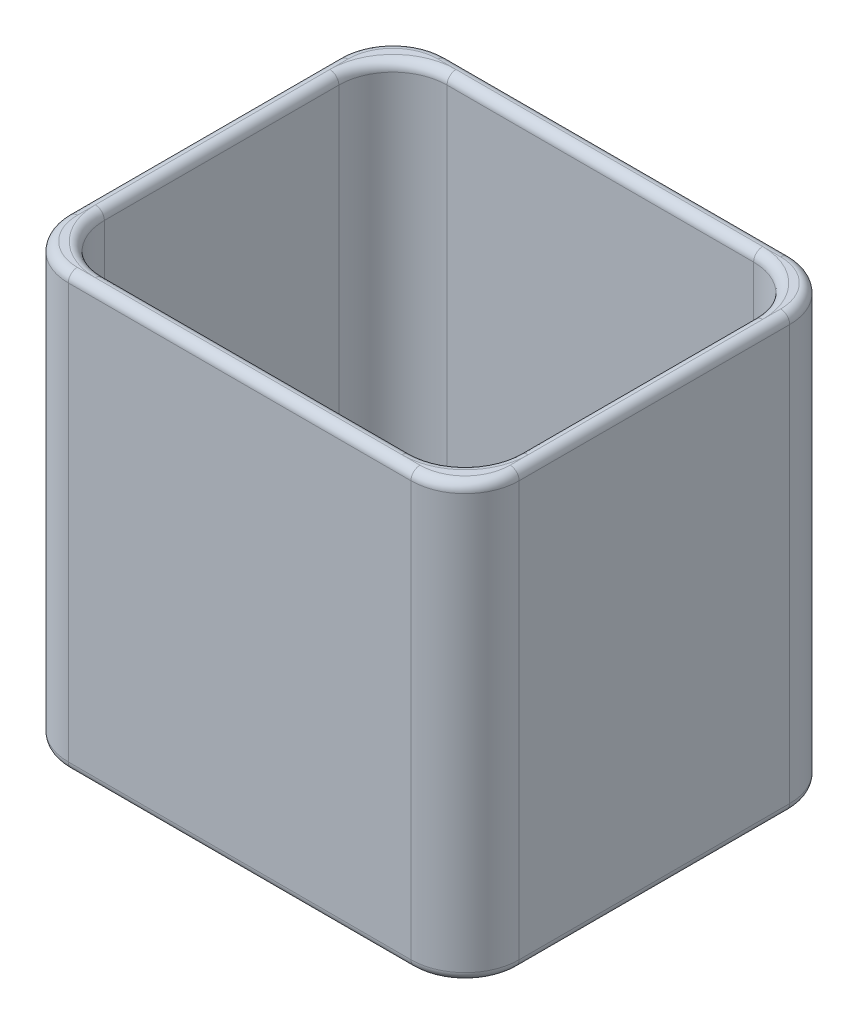
SolidWorks part; units mm, degrees
ref_plane "Front Plane" through (0, 0, 0) normal (0, 0, 1) x (1, 0, 0)
ref_plane "Top Plane" through (0, 0, 0) normal (0, 1, 0) x (1, 0, 0)
ref_plane "Right Plane" through (0, 0, 0) normal (1, 0, 0) x (0, 0, -1)
sketch "Sketch1" plane through (0, 0, 0) normal (0, 1, 0) x (1, 0, 0)
  line L1 (-36.5125, -30.1625) -> (36.5125, -30.1625)
  line L2 (-36.5125, -30.1625) -> (-36.5125, 30.1625)
  line L3 (-36.5125, 30.1625) -> (36.5125, 30.1625)
  line L4 (36.5125, -30.1625) -> (36.5125, 30.1625)
  line L5 (-36.5125, -30.1625) -> (36.5125, 30.1625) construction
  line L6 (-36.5125, 30.1625) -> (36.5125, -30.1625) construction
  point P0 (0, 0)
  dimension "D1" = 73.025
  dimension "D2" = 60.325
extrude "Extrude-Thin1" add sketch "Sketch1" along normal blind 73.025 thin thin type one direction wall 3.175
fillet "Fillet1" radius 9.525 8 edges at (-36.5125, 36.5125, 30.1625) (36.5125, 36.5125, 30.1625) (36.5125, 36.5125, -30.1625) (39.6875, 36.5125, 33.3375) (-39.6875, 36.5125, 33.3375) (-39.6875, 36.5125, -33.3375) (39.6875, 36.5125, -33.3375) (-36.5125, 36.5125, -30.1625)
sketch "Sketch2" plane through (0, 0, 0) normal (0, -1, 0) x (1, 0, 0)
  line L4 (39.6875, -23.8125) -> (39.6875, 23.8125)
  line L5 (30.1625, 33.3375) -> (-30.1625, 33.3375)
  line L6 (-39.6875, 23.8125) -> (-39.6875, -23.8125)
  line L7 (-30.1625, -33.3375) -> (30.1625, -33.3375)
  line L8 (39.6875, -23.8125) -> (39.6875, 23.8125)
  line L9 (30.1625, 33.3375) -> (-30.1625, 33.3375)
  line L10 (-39.6875, 23.8125) -> (-39.6875, -23.8125)
  line L11 (-30.1625, -33.3375) -> (30.1625, -33.3375)
  arc A4 (39.6875, 23.8125) -> (30.1625, 33.3375) centre (30.1625, 23.8125) ccw
  arc A5 (-30.1625, 33.3375) -> (-39.6875, 23.8125) centre (-30.1625, 23.8125) ccw
  arc A6 (-39.6875, -23.8125) -> (-30.1625, -33.3375) centre (-30.1625, -23.8125) ccw
  arc A7 (30.1625, -33.3375) -> (39.6875, -23.8125) centre (30.1625, -23.8125) ccw
  arc A8 (39.6875, 23.8125) -> (30.1625, 33.3375) centre (30.1625, 23.8125) ccw
  arc A9 (-30.1625, 33.3375) -> (-39.6875, 23.8125) centre (-30.1625, 23.8125) ccw
  arc A10 (-39.6875, -23.8125) -> (-30.1625, -33.3375) centre (-30.1625, -23.8125) ccw
  arc A11 (30.1625, -33.3375) -> (39.6875, -23.8125) centre (30.1625, -23.8125) ccw
  dimension "D1" = 0
extrude "Boss-Extrude1" add sketch "Sketch2" along normal blind 3.175
fillet "Fillet2" radius 6.35 8 edges at (0, 0, -30.1625) (33.7227, 0, -27.3727) (36.5125, 0, 0) (33.7227, 0, 27.3727) (0, 0, 30.1625) (-33.7227, 0, 27.3727) (-36.5125, 0, 0) (-33.7227, 0, -27.3727)
fillet "Fillet3" radius 1.5875 24 edges at (-36.8977, 73.025, 30.5477) (-39.6875, 73.025, 0) (-36.8977, 73.025, -30.5477) (0, 73.025, -33.3375) (36.8977, 73.025, -30.5477) (39.6875, 73.025, 0) (36.8977, 73.025, 30.5477) (-33.7227, 73.025, -27.3727) (0, 73.025, -30.1625) (33.7227, 73.025, -27.3727) (36.5125, 73.025, 0) (33.7227, 73.025, 27.3727) (0, 73.025, 30.1625) (-33.7227, 73.025, 27.3727) (0, 73.025, 33.3375) (-36.5125, 73.025, 0) (-36.8977, -3.175, 30.5477) (0, -3.175, 33.3375) (36.8977, -3.175, 30.5477) (39.6875, -3.175, 0) (36.8977, -3.175, -30.5477) (0, -3.175, -33.3375) (-36.8977, -3.175, -30.5477) (-39.6875, -3.175, 0)
sketch "Sketch3" plane through (0, 0, 0) normal (0, 1, 0) x (1, 0, 0)
  line L0 (-25.4, 19.05) -> (-26.9875, 20.6375) construction
  line L1 (0, 0) -> (-25.4, 0) construction
  line L2 (0, 0) -> (0, 19.05) construction
  line L3 (0, 19.05) -> (-25.4, 19.05) construction
  line L4 (-25.4, 0) -> (-25.4, 19.05) construction
  point P5 (-26.9875, 20.6375)
  dimension "D1" = 45
  dimension "D2" = 1.5875
ref_axis "Axis1" through (-25.4, 0, -19.05) along (0, 1, 0)
ref_plane "Plane1" through (0, 0, -19.05) normal (0, 0, -1) x (0, 1, 0)
sketch "Sketch4" plane through (0, 0, -19.05) normal (0, 0, -1) x (0, 1, 0)
  line L0 (-3.175, -23.3362) -> (-1.24, -23.3362)
  line L1 (-3.175, -30.1625) -> (-3.175, 30.1625) construction
  line L2 (-1.24, -23.3362) -> (0, -21.2725)
  line L3 (0, -21.2725) -> (0, -25.4)
  line L4 (0, -25.4) -> (25.3633, -25.4) construction
  line L5 (0, -25.4) -> (-3.175, -25.4) construction
  line L6 (-3.175, -25.4) -> (-3.175, -23.3362)
  line L8 (0, 0) -> (0, -25.4) construction
  line L9 (0, -25.4) -> (-3.175, -25.4)
  point P4 (2.519, -23.2861)
  dimension "D1" = 59
  dimension "D2" = 8.255
  dimension "D3" = 4.1275
revolve "Cut-Revolve1" cut sketch "Sketch4" angle 360 about L5
mirror "Mirror1" about plane through (0, 0, 0) normal (1, 0, 0) of "Cut-Revolve1"
mirror "Mirror2" about plane through (0, 0, 0) normal (0, 0, 1) of "Cut-Revolve1", "Mirror1"
